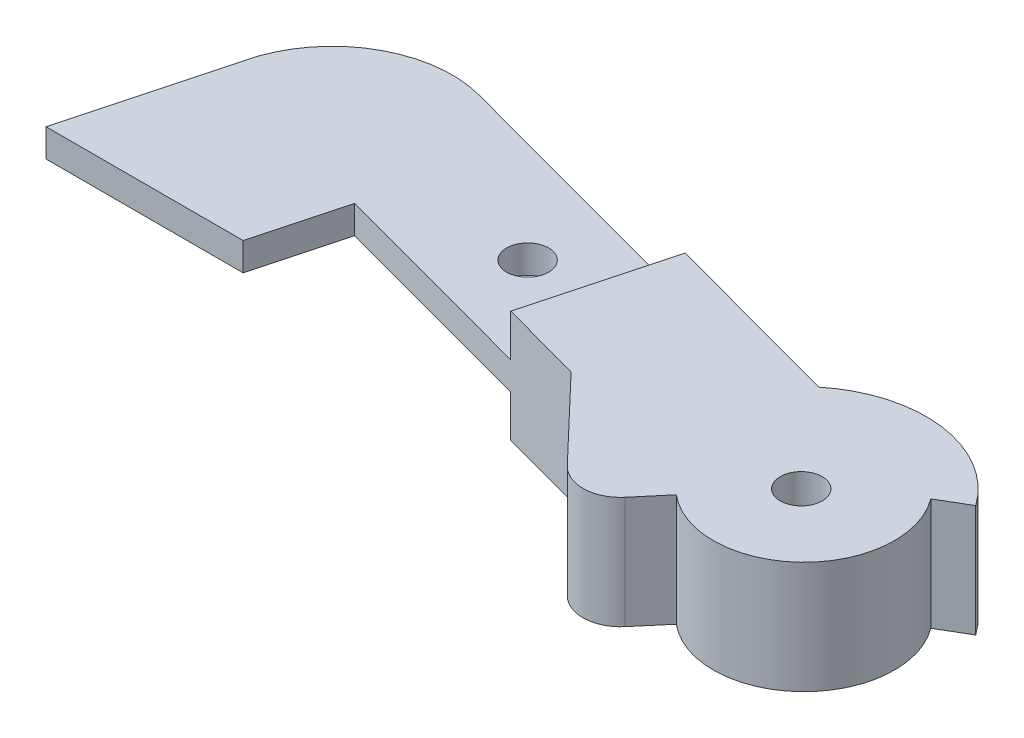
SolidWorks part; units mm, degrees
ref_plane "Front Plane" through (0, 0, 0) normal (0, 0, 1) x (1, 0, 0)
ref_plane "Top Plane" through (0, 0, 0) normal (0, 1, 0) x (1, 0, 0)
ref_plane "Right Plane" through (0, 0, 0) normal (1, 0, 0) x (0, 0, -1)
sketch "Sketch1" plane through (0, 0, 0) normal (0, 1, 0) x (1, 0, 0)
  line L0 (35.6193, 13.423) -> (40.6193, 13.423) construction
  line L1 (0, 0) -> (21.0971, 0)
  line L2 (21.0971, 0) -> (23.6219, 9.4045)
  line L3 (23.6219, 9.4045) -> (55.3156, 0.8959)
  line L4 (55.3156, 0.8959) -> (63.8377, -8.039)
  line L5 (89.3835, 10.135) -> (86.3533, 8.3579)
  line L6 (72.3541, -4.8889) -> (69.838, -7.8612)
  line L7 (70.0121, 12.7254) -> (20.2818, 26.1035)
  line L8 (0, 0) -> (4.7941, 17.8578)
  circle A0 centre (38.1375, 13.4144) radius 2.25
  arc A1 (63.8377, -8.039) -> (69.838, -7.8612) centre (66.7579, -5.2538) ccw
  circle A2 centre (78.4844, 2.3565) radius 2.25
  arc A3 (72.3541, -4.8889) -> (86.3533, 8.3579) centre (78.5876, 2.5441) ccw
  arc A4 (89.3835, 10.135) -> (70.0121, 12.7254) centre (78.4844, 2.3565) ccw
  arc A6 (20.2818, 26.1035) -> (4.3466, 16.1906) centre (16.9456, 13.7019) ccw
  point P10 (70.0121, 12.7254)
  dimension "D2" = 4.5
  dimension "D3" = 4.5
  dimension "D1" = 5
  dimension "D4" = 41.8852
extrude "Boss-Extrude1" add sketch "Sketch1" along normal blind 3 contours L7 A6 L8 L1 L2 L3 L4 A1 L6 A3 L5 A4 A0 A2 region at (44.3008, 0, -9.3123)
sketch "Sketch6" plane through (0, 3, 0) normal (0, 1, 0) x (1, 0, 0)
  line L0 (27.3951, 24.0179) -> (32.3951, 24.0179) construction
  line L3 (46.4668, 3.2715) -> (55.3156, 0.8959)
  line L4 (55.3156, 0.8959) -> (63.8377, -8.039)
  line L5 (89.3835, 10.135) -> (86.3533, 8.3579)
  line L6 (72.3541, -4.8889) -> (69.838, -7.8612)
  line L7 (70.0121, 12.7254) -> (50.4273, 17.994)
  line L9 (46.4668, 3.2715) -> (50.4273, 17.994)
  arc A1 (63.8377, -8.039) -> (69.838, -7.8612) centre (66.7579, -5.2538) ccw
  circle A2 centre (78.4844, 2.3565) radius 2.25
  arc A3 (72.3541, -4.8889) -> (86.3533, 8.3579) centre (78.5876, 2.5441) ccw
  arc A4 (89.3835, 10.135) -> (70.0121, 12.7254) centre (78.4844, 2.3565) ccw
  point P10 (70.0121, 12.7254)
  dimension "D3" = 4.5
  dimension "D1" = 5
extrude "Boss-Extrude3" add sketch "Sketch6" along normal blind 4.5 contours L3 L4 A1 L6 A3 L5 A4 L7 L9 | A2
extrude "Boss-Extrude4" add sketch "Sketch6<4>" against normal blind 4.5 from surface starting at face at (38.1375, 0, -11.1644)
sketch "Sketch6<4>" plane through (0, 3, 0) normal (0, 1, 0) x (1, 0, 0) same geometry as "Sketch6"
